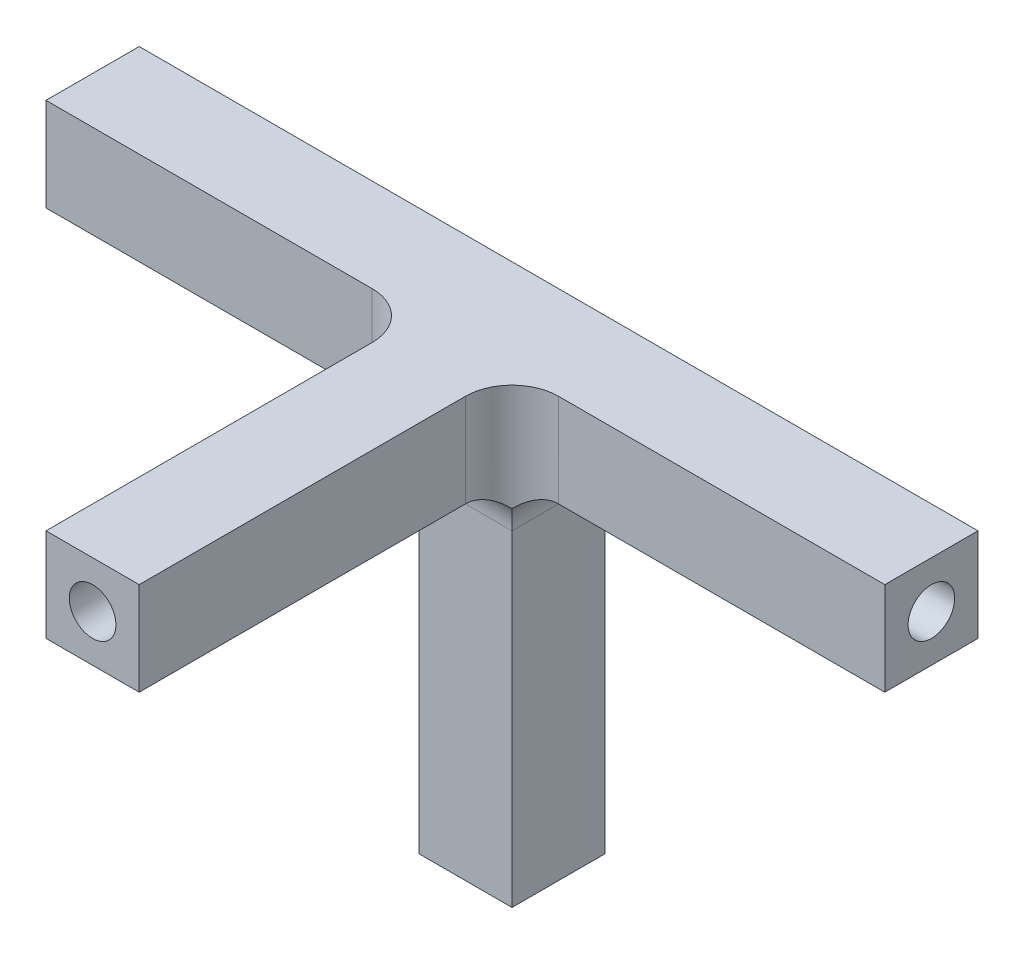
SolidWorks part; units mm, degrees
ref_plane "Front Plane" through (0, 0, 0) normal (0, 0, 1) x (1, 0, 0)
ref_plane "Top Plane" through (0, 0, 0) normal (0, 1, 0) x (1, 0, 0)
ref_plane "Right Plane" through (0, 0, 0) normal (1, 0, 0) x (0, 0, -1)
sketch "Sketch1" plane through (0, 0, 0) normal (0, 0, 1) x (1, 0, 0)
  line L0 (-9, 1) -> (9, 1)
  line L1 (9, 1) -> (9, -1)
  line L2 (9, -1) -> (1, -1)
  line L3 (1, -1) -> (1, -9)
  line L4 (1, -9) -> (-1, -9)
  line L5 (-1, -9) -> (-1, -1)
  line L6 (-1, -1) -> (-9, -1)
  line L7 (-9, -1) -> (-9, 1)
  point P3 (0, -9)
  point P9 (-9, 0)
  dimension "D1" = 8
  dimension "D2" = 2
extrude "Boss-Extrude1" add sketch "Sketch1" along normal mid plane 2
sketch "Sketch2" plane through (0, 0, 0) normal (1, 0, 0) x (0, 0, -1)
  circle A0 centre (0, 0) radius 0.5
  dimension "D1" = 1
extrude "Cut-Extrude1" cut sketch "Sketch2" against normal through all both and the other way through all
sketch "Sketch3" plane through (0, 0, 0) normal (0, 1, 0) x (1, 0, 0)
  circle A0 centre (0, 0) radius 0.5
  dimension "D1" = 1
extrude "Cut-Extrude2" cut sketch "Sketch3" against normal up to surface (9 mm away) up to face at (0, -9, 0)
sketch "Sketch7" plane through (0, 0, 1) normal (0, 0, 1) x (1, 0, 0)
  line L0 (9, 1) -> (-9, 1) construction
  line L1 (-1, -1) -> (1, -1)
  line L2 (-1, -1) -> (-1, 1)
  line L3 (-1, 1) -> (1, 1)
  line L4 (1, -1) -> (1, 1)
  line L5 (1, -9) -> (1, -1) construction
  circle A0 centre (0, 0) radius 0.5
  line M12 (9, 1) -> (-9, 1)
  dimension "D1" = 1
extrude "Boss-Extrude2" add sketch "Sketch7" along normal blind 8 contours A0 | L1 L4 L2 A0 M12 region at (-0.9717, 0, 1) region at (0, 0, 1)
extrude "Cut-Extrude6" cut sketch "Sketch7<4>" along normal blind 8 and the other way blind 1 contours A0 region at (0, 0, 1)
sketch "Sketch7<4>" plane through (0, 0, 1) normal (0, 0, 1) x (1, 0, 0) same geometry as "Sketch7"
sketch "Sketch4" plane through (0, 0, 0) normal (1, 0, 0) x (0, 0, -1)
  line L0 (0, 1) -> (0, -9)
  line L1 (-1, 1) -> (1, 1) construction
  line L2 (-1, -9) -> (1, -9) construction
  line L3 (0, -9) -> (-1, -9)
  line L4 (-1, -9) -> (-1, 1)
  line L5 (-1, 1) -> (0, 1)
sketch "Sketch5" plane through (0, 0, 0) normal (0, 0, 1) x (1, 0, 0)
  line L0 (-9, 1) -> (-9, -1) construction
  line L1 (-9, 0.5) -> (-6, 0.5)
  line L2 (-9, 0.5) -> (-9, -0.5)
  line L3 (-9, -0.5) -> (-6, -0.5)
  line L4 (-6, 0.5) -> (-6, -0.5)
  point P6 (-6, 0)
  dimension "D1" = 3
sketch "Sketch6" plane through (0, 0, 1) normal (0, 0, 1) x (1, 0, 0)
  line L0 (-1, -9) -> (1, -9) construction
  line L1 (-0.5, -9) -> (0.5, -9)
  line L2 (-0.5, -9) -> (-0.5, -6)
  line L3 (-0.5, -6) -> (0.5, -6)
  line L4 (0.5, -9) -> (0.5, -6)
  point P6 (0, -6)
  dimension "D1" = 3
fillet "Fillet3" radius 1 2 edges at (-1, -1, 0) (1, -1, 0)
fillet "Fillet4" radius 1 2 edges at (1, 0, 1) (-1, 0, 1)
fillet "Fillet5" radius 1 1 edges at (0, -1, 1)
